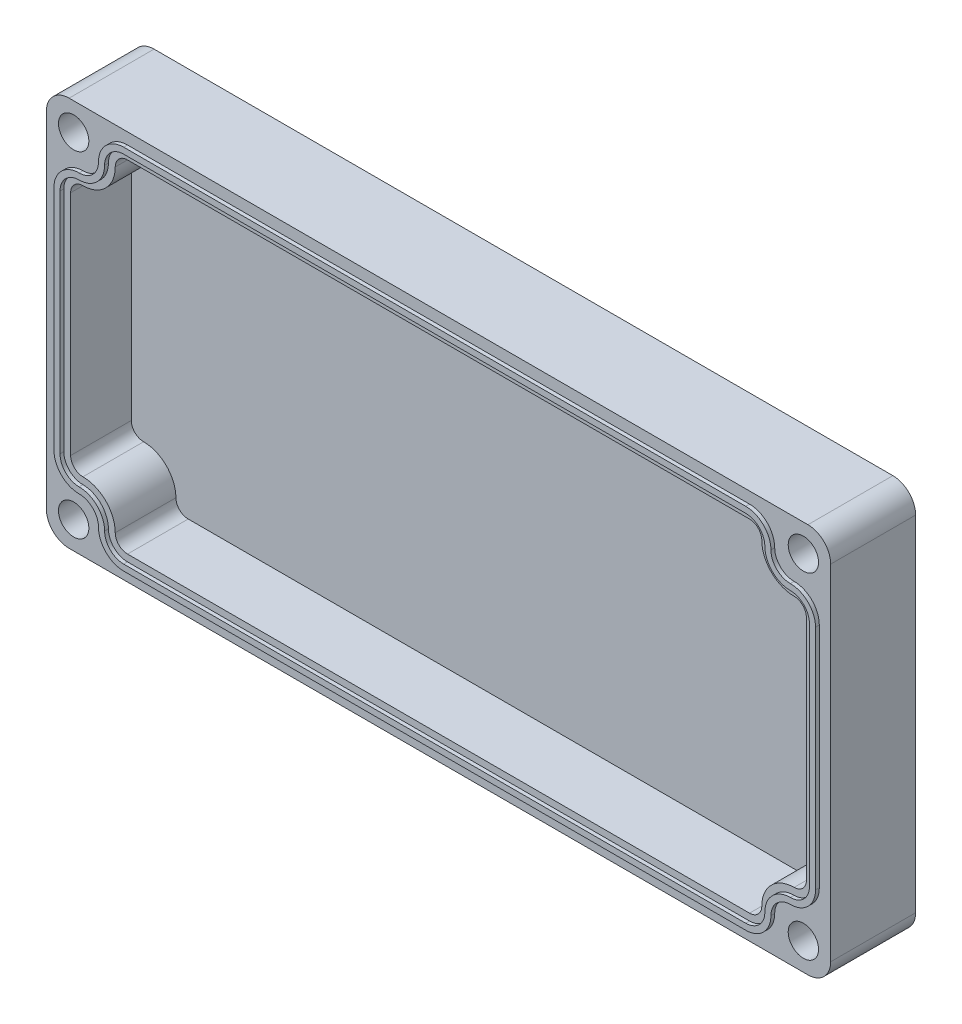
SolidWorks part; units mm, degrees
ref_plane "Plan de face" through (0, 0, 0) normal (0, 0, 1) x (1, 0, 0)
ref_plane "Plan de dessus" through (0, 0, 0) normal (0, 1, 0) x (1, 0, 0)
ref_plane "Plan de droite" through (0, 0, 0) normal (1, 0, 0) x (0, 0, -1)
sketch "Esquisse1" plane through (0, 0, 0) normal (0, 0, 1) x (1, 0, 0)
  line L1 (-48.5, 22.5) -> (48.5, 22.5)
  line L2 (-48.5, 22.5) -> (-48.5, -22.5)
  line L3 (-48.5, -22.5) -> (48.5, -22.5)
  line L4 (48.5, 22.5) -> (48.5, -22.5)
  line L5 (-48.5, 22.5) -> (48.5, -22.5) construction
  line L6 (-48.5, -22.5) -> (48.5, 22.5) construction
  point P0 (0, 0)
  dimension "D1" = 97
  dimension "D2" = 45
extrude "Boss.-Extru.1" add sketch "Esquisse1" along normal blind 8
shell "Coque1" thickness 3.2 removed face at (0, 0, 8) outward yes
ref_plane "Plan1" through (0, 0, 20) normal (0, 0, 1) x (1, 0, 0)
sketch "Esquisse10" plane through (0, 0, 0) normal (0, 0, 1) x (1, 0, 0)
  line L0 (-48.5, 22.5) -> (-48.5, 15)
  line L1 (-48.5, 22.5) -> (-48.5, -22.5) construction
  line L2 (48.5, 22.5) -> (-48.5, 22.5) construction
  line L3 (-41, 22.5) -> (-48.5, 22.5)
  line L4 (-46.88, 15) -> (-48.5, 15) construction
  line L5 (-46.88, 15) -> (-46.88, 16.62) construction
  line L6 (-41, 20.88) -> (-42.62, 20.88) construction
  line L7 (-41, 20.88) -> (-41, 22.5) construction
  arc A1 (-48.5, 15) -> (-46.88, 16.62) centre (-46.88, 15) cw
  arc A2 (-46.88, 16.62) -> (-42.62, 20.88) centre (-46.88, 20.88) ccw
  arc A3 (-42.62, 20.88) -> (-41, 22.5) centre (-41, 20.88) cw
  dimension "D1" = 7.5
extrude "Boss.-Extru.2" add sketch "Esquisse10" along normal up to surface (8 mm away) up to face at (0, 0, 8)
mirror "Symétrie1" about plane through (0, 0, 0) normal (1, 0, 0) of "Boss.-Extru.2"
mirror "Symétrie2" about plane through (0, 0, 0) normal (0, 1, 0) of "Boss.-Extru.2"
mirror "Symétrie3" about plane through (0, 0, 0) normal (0, 1, 0) of "Symétrie1"
sketch "Esquisse13" plane through (0, 0, 8) normal (0, 0, 1) x (1, 0, 0)
  line L0 (-48.1, 22.1) -> (-48.1, 24.1) construction
  line L1 (51.7, 25.7) -> (-51.7, 25.7) construction
  line L2 (-48.1, 22.1) -> (-50.1, 22.1) construction
  line L4 (-51.7, 25.7) -> (-51.7, -25.7) construction
  circle A0 centre (-48.1, 22.1) radius 2
  circle A1 centre (-48.1, 22.1) radius 2.75 construction
  dimension "D1" = 4
  dimension "D4" = 5.5
  dimension "D2" = 1.6
  dimension "D3" = 1.6
extrude "Insert" cut sketch "Esquisse13" against normal up to next
mirror "Symétrie4" about plane through (0, 0, 0) normal (1, 0, 0) of "Insert"
mirror "Symétrie5" about plane through (0, 0, 0) normal (0, 1, 0) of "Symétrie4"
sketch "Esquisse14" plane through (0, 0, 8) normal (0, 0, 1) x (1, 0, 0)
  line L0 (-41, 22.5) -> (41, 22.5) construction
  line L1 (48.5, 15) -> (48.5, -15) construction
  line L2 (41, -22.5) -> (-41, -22.5) construction
  line L3 (-48.5, -15) -> (-48.5, 15) construction
  line L4 (-50.1, -15) -> (-50.1, 15) construction
  line L5 (-41, 24.1) -> (41, 24.1) construction
  line L6 (50.1, 15) -> (50.1, -15) construction
  line L7 (41, -24.1) -> (-41, -24.1) construction
  line L8 (-41, 23.4) -> (41, 23.4)
  line L9 (49.4, 15) -> (49.4, -15)
  line L10 (41, -23.4) -> (-41, -23.4)
  line L11 (-49.4, -15) -> (-49.4, 15)
  arc A0 (41, 22.5) -> (42.62, 20.88) centre (41, 20.88) cw construction
  arc A1 (42.62, 20.88) -> (46.88, 16.62) centre (46.88, 20.88) ccw construction
  arc A2 (46.88, 16.62) -> (48.5, 15) centre (46.88, 15) cw construction
  arc A3 (48.5, -15) -> (46.88, -16.62) centre (46.88, -15) cw construction
  arc A4 (46.88, -16.62) -> (42.62, -20.88) centre (46.88, -20.88) ccw construction
  arc A5 (42.62, -20.88) -> (41, -22.5) centre (41, -20.88) cw construction
  arc A6 (-41, -22.5) -> (-42.62, -20.88) centre (-41, -20.88) cw construction
  arc A7 (-42.62, -20.88) -> (-46.88, -16.62) centre (-46.88, -20.88) ccw construction
  arc A8 (-46.88, -16.62) -> (-48.5, -15) centre (-46.88, -15) cw construction
  arc A9 (-48.5, 15) -> (-46.88, 16.62) centre (-46.88, 15) cw construction
  arc A10 (-46.88, 16.62) -> (-42.62, 20.88) centre (-46.88, 20.88) ccw construction
  arc A11 (-42.62, 20.88) -> (-41, 22.5) centre (-41, 20.88) cw construction
  arc A12 (-50.1, 15) -> (-46.88, 18.22) centre (-46.88, 15) cw construction
  arc A13 (-46.88, 18.22) -> (-44.22, 20.88) centre (-46.88, 20.88) ccw construction
  arc A14 (-44.22, 20.88) -> (-41, 24.1) centre (-41, 20.88) cw construction
  arc A15 (41, 24.1) -> (44.22, 20.88) centre (41, 20.88) cw construction
  arc A16 (44.22, 20.88) -> (46.88, 18.22) centre (46.88, 20.88) ccw construction
  arc A17 (46.88, 18.22) -> (50.1, 15) centre (46.88, 15) cw construction
  arc A18 (50.1, -15) -> (46.88, -18.22) centre (46.88, -15) cw construction
  arc A19 (46.88, -18.22) -> (44.22, -20.88) centre (46.88, -20.88) ccw construction
  arc A20 (44.22, -20.88) -> (41, -24.1) centre (41, -20.88) cw construction
  arc A21 (-41, -24.1) -> (-44.22, -20.88) centre (-41, -20.88) cw construction
  arc A22 (-44.22, -20.88) -> (-46.88, -18.22) centre (-46.88, -20.88) ccw construction
  arc A23 (-46.88, -18.22) -> (-50.1, -15) centre (-46.88, -15) cw construction
  arc A24 (-43.52, 20.88) -> (-41, 23.4) centre (-41, 20.88) cw
  arc A25 (41, 23.4) -> (43.52, 20.88) centre (41, 20.88) cw
  arc A26 (43.52, 20.88) -> (46.88, 17.52) centre (46.88, 20.88) ccw
  arc A27 (46.88, 17.52) -> (49.4, 15) centre (46.88, 15) cw
  arc A28 (49.4, -15) -> (46.88, -17.52) centre (46.88, -15) cw
  arc A29 (46.88, -17.52) -> (43.52, -20.88) centre (46.88, -20.88) ccw
  arc A30 (43.52, -20.88) -> (41, -23.4) centre (41, -20.88) cw
  arc A31 (-41, -23.4) -> (-43.52, -20.88) centre (-41, -20.88) cw
  arc A32 (-43.52, -20.88) -> (-46.88, -17.52) centre (-46.88, -20.88) ccw
  arc A33 (-46.88, -17.52) -> (-49.4, -15) centre (-46.88, -15) cw
  arc A34 (-49.4, 15) -> (-46.88, 17.52) centre (-46.88, 15) cw
  arc A35 (-46.88, 17.52) -> (-43.52, 20.88) centre (-46.88, 20.88) ccw
  dimension "D1" = 1.6
  dimension "D2" = 0.9
extrude "Extru.-Mince1" add sketch "Esquisse14" along normal blind 0.5 thin thin type one direction wall 0.8
fillet "Congé1" radius 3 4 edges at (-51.7, -25.7, 2.4) (51.7, -25.7, 2.4) (51.7, 25.7, 2.4) (-51.7, 25.7, 2.4)
sketch "Esquisse15" plane through (0, 0, -3.2) normal (0, 0, -1) x (-1, 0, 0)
  line L0 (36.5677, 119.0943) -> (94.262, 119.0943) construction
  line L1 (52.6667, 130) -> (263.3333, 130) construction
equation "\"buse\"= 0.8"
equation "\"D1@Coque1\"=\"buse\"*4"
equation "\"hauteur\"=10"
equation "\"D1@Nervure1\"=\"hauteur\""
equation "\"D1@Nervure18\"=\"buse\""
equation "\"D2@Esquisse13\"=\"buse\"*2"
equation "\"D3@Esquisse13\"=2*\"buse\""
equation "\"D2@Esquisse14\"=\"buse\"+0.1"
